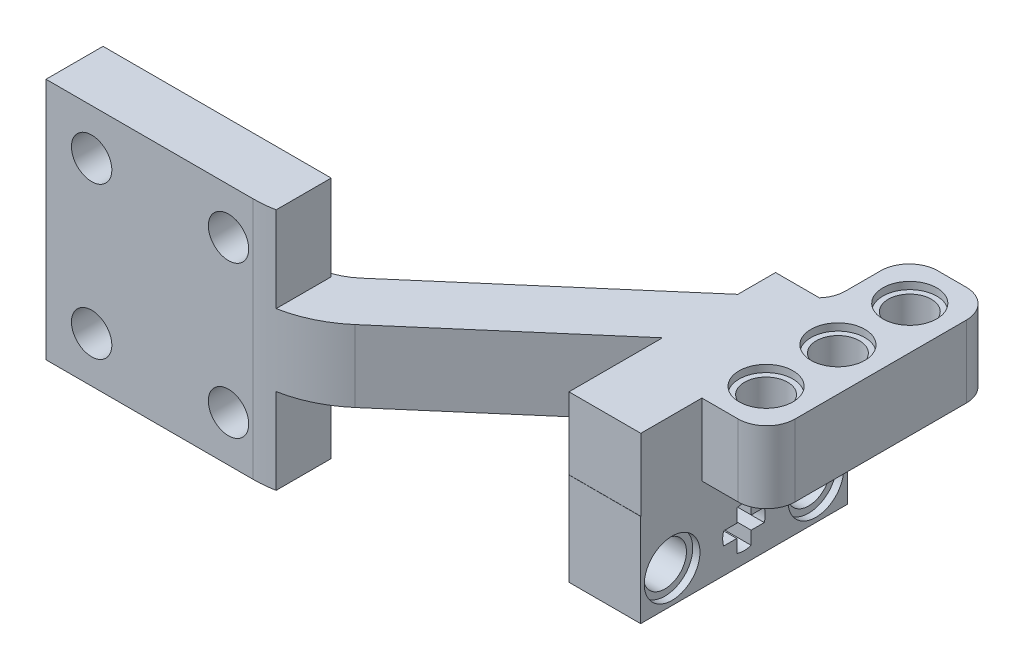
SolidWorks part; units mm, degrees
ref_plane "Front Plane" through (0, 0, 0) normal (0, 0, 1) x (1, 0, 0)
ref_plane "Top Plane" through (0, 0, 0) normal (0, 1, 0) x (1, 0, 0)
ref_plane "Right Plane" through (0, 0, 0) normal (1, 0, 0) x (0, 0, -1)
sketch "Sketch6" plane through (0, 0, 0) normal (0, 1, 0) x (1, 0, 0)
  line L1 (-4.7625, 12.7) -> (4.7625, 12.7)
  line L2 (-4.7625, 12.7) -> (-4.7625, -12.7)
  line L3 (-4.7625, -12.7) -> (4.7625, -12.7)
  line L4 (4.7625, 12.7) -> (4.7625, -12.7)
  line L5 (-4.7625, 12.7) -> (4.7625, -12.7) construction
  line L6 (-4.7625, -12.7) -> (4.7625, 12.7) construction
  point P0 (0, 0)
  dimension "D1" = 9.525
  dimension "D2" = 25.4
extrude "Boss-Extrude1" add sketch "Sketch6" against normal blind 8
sketch "Sketch16" plane through (0, 0, 0) normal (0, -1, 0) x (1, 0, 0)
  line L1 (-2.4423, -3.5) -> (-10.4423, -3.5)
  line L2 (-2.4423, -3.5) -> (-2.4423, 19.5)
  line L3 (-2.4423, 19.5) -> (-10.4423, 19.5)
  line L4 (-10.4423, -3.5) -> (-10.4423, 19.5)
  line L5 (-2.4423, -3.5) -> (-10.4423, 19.5) construction
  line L6 (-2.4423, 19.5) -> (-10.4423, -3.5) construction
  line L7 (-4.7625, -12.7) -> (-4.7625, 12.7) construction
  point P0 (-6.4423, 8)
  point P12 (-4.7625, 0)
  dimension "D1" = 6.4423
  dimension "D2" = 8
  dimension "D3" = 8
  dimension "D4" = 23
extrude "Boss-Extrude6" add sketch "Sketch16" along normal up to surface (8 mm away) up to face at (0, -8, 0)
sketch "Sketch7" plane through (0, 0, 0) normal (0, 1, 0) x (1, 0, 0)
  circle A0 centre (0, 8) radius 2.4
  circle A1 centre (0, 0) radius 2.4
  circle A2 centre (0, -8) radius 2.4
  circle A3 centre (0, 8) radius 3
  circle A4 centre (0, 0) radius 3
  circle A5 centre (0, -8) radius 3
  dimension "D3" = 4.8
  dimension "D1" = 8
  dimension "D2" = 8
  dimension "D4" = 0.6
extrude "Cut-Extrude1" cut sketch "Sketch7" against normal blind 0.8
extrude "Cut-Extrude2" cut sketch "Sketch7<3>" against normal blind 7.2 contours A0 | A1 | A2 region at (0, 0, -8) region at (0, 0, 0) region at (0, 0, 8)
sketch "Sketch7<3>" plane through (0, 0, 0) normal (0, 1, 0) x (1, 0, 0) same geometry as "Sketch7"
sketch "Sketch9" plane through (0, -7.2, -7.2) normal (0, 1, 0) x (1, 0, 0)
  circle A0 centre (0, 0.8) radius 2.4
  circle A1 centre (0, -7.2) radius 2.4
  circle A2 centre (0, -15.2) radius 2.4
  circle A3 centre (0, 0.8) radius 3
  circle A4 centre (0, -7.2) radius 3
  circle A5 centre (0, -15.2) radius 3
  dimension "D3" = 4.8
  dimension "D1" = 8
  dimension "D2" = 8
  dimension "D4" = 0.6
extrude "Cut-Extrude4" cut sketch "Sketch9" against normal blind 0.8 contours A3 | A4 | A5
ref_plane "Plane4" through (0, 0, 28) normal (0, 0, 1) x (1, 0, 0)
sketch "Sketch10" plane through (0, -8, 0) normal (0, -1, 0) x (-1, 0, 0)
  line L1 (4.7625, 4.1904) -> (34.7625, -21.65)
  line L2 (4.7625, 4.1904) -> (4.7625, -4.1904) construction
  line L3 (34.7625, -21.65) -> (60.1625, -21.65)
  line L4 (60.1625, -21.65) -> (60.1625, -28)
  line L5 (-57.9984, -28) -> (57.9984, -28) construction
  line L8 (4.7625, -4.1904) -> (32.4047, -28)
  line L10 (4.7625, 4.1904) -> (4.7625, -4.1904)
  line L14 (4.7625, 12.7) -> (4.7625, 3.5) construction
  line L18 (32.4047, -28) -> (60.1625, -28)
  point P2 (4.7625, 0)
  dimension "D1" = 30
  dimension "D2" = 6.35
  dimension "D3" = 25.4
  dimension "D4" = 6.35
extrude "Boss-Extrude3" add sketch "Sketch10" against normal up to surface (8 mm away) up to face at (0, 0, -5)
fillet "Fillet1" radius 3.175 1 edges at (-4.7625, -4, -4.1904)
fillet "Fillet3" radius 3.175 3 edges at (4.7625, -4, -12.7) (4.7625, -4, 12.7) (-4.7625, -4, -12.7)
sketch "Sketch18" plane through (0, 0, 0) normal (0, 1, 0) x (1, 0, 0)
  line L0 (-57.9984, -28) -> (57.9984, -28) construction
  line L1 (-60.1625, -21.65) -> (-34.7625, -21.65)
  line L2 (-60.1625, -21.65) -> (-60.1625, -28)
  line L3 (-60.1625, -28) -> (-34.7625, -28)
  line L4 (-34.7625, -21.65) -> (-34.7625, -28)
extrude "Boss-Extrude7" add sketch "Sketch18" along normal blind 9.525 and the other way blind 17.525
fillet "Fillet6" radius 12.7 1 edges at (-32.4047, -4, 28)
fillet "Fillet7" radius 6.35 1 edges at (-34.7625, -4, 21.65)
sketch "Sketch11" plane through (0, -8, 0) normal (0, -1, 0) x (-1, 0, 0)
  line L0 (4.7625, 9.525) -> (4.7625, 5.6089) construction
  line L1 (10.4422, -19.5186) -> (2.4422, -19.5186)
  line L2 (10.4422, -19.5186) -> (10.4422, 3.4814)
  line L3 (10.4422, 3.4814) -> (2.4422, 3.4814)
  line L4 (2.4422, -19.5186) -> (2.4422, 3.4814)
  line L5 (10.4422, -19.5186) -> (2.4422, 3.4814) construction
  line L6 (10.4422, 3.4814) -> (2.4422, -19.5186) construction
  point P0 (6.4422, -8.0186)
  point P9 (4.7625, 7.5669)
  dimension "D1" = 6.4422
  dimension "D2" = 15.5855
  dimension "D3" = 8
  dimension "D4" = 23
extrude "Boss-Extrude4" add sketch "Sketch11" along normal blind 6.7462 contours L4 L3 L2 L1
sketch "Sketch13" plane through (-2.4423, 0, 0) normal (1, 0, 0) x (0, 0, -1)
  line L0 (-19.5186, -14.7462) -> (3.4814, -14.7462) construction
  line L1 (-8.8186, -14.0148) -> (-8.8186, -12.5521)
  line L2 (-7.2186, -12.5521) -> (-7.2186, -14.0148)
  line L3 (-8.8186, -14.0148) -> (-7.2186, -14.0148) construction
  line L4 (-8.8186, -14.0148) -> (-8.8186, -15.4775) construction
  line L5 (-8.8186, -14.0148) -> (-10.2813, -14.0148)
  line L6 (-10.2813, -15.4775) -> (-8.8186, -15.4775)
  line L7 (-8.8186, -15.4775) -> (-8.8186, -16.9403)
  line L8 (-7.2186, -16.9403) -> (-7.2186, -15.4775)
  line L9 (-7.2186, -15.4775) -> (-5.7558, -15.4775)
  line L10 (-7.2186, -14.0148) -> (-5.7558, -14.0148)
  line L11 (-5.7558, -14.0148) -> (-5.9183, -14.0148)
  circle A0 centre (-8.0186, -14.7462) radius 2.5157 construction
  circle A1 centre (-16.0186, -14.7462) radius 3.1
  circle A2 centre (-0.0186, -14.7462) radius 3.1
  circle A3 centre (-16.0186, -14.7462) radius 2.4
  circle A4 centre (-0.0186, -14.7462) radius 2.4
  arc A5 (-8.8186, -12.5521) -> (-7.2186, -12.5521) centre (-8.0186, -15.0259) cw
  arc A6 (-10.2813, -14.0148) -> (-10.2813, -15.4775) centre (-7.7863, -14.7462) ccw
  arc A7 (-8.8186, -16.9403) -> (-7.2186, -16.9403) centre (-8.0186, -14.4664) ccw
  arc A8 (-5.7558, -14.0148) -> (-5.7558, -15.4775) centre (-8.2509, -14.7462) cw
  point P14 (-8.0186, -14.0148)
  point P16 (-8.8186, -14.7462)
  line M4 (-19.5186, -14.7462) -> (3.4814, -14.7462)
  dimension "D1" = 6.2
  dimension "D2" = 4.8
  dimension "D7" = 2.6
  dimension "D3" = 8
  dimension "D4" = 8
  dimension "D5" = 1.4627
  dimension "D6" = 1.6
sketch "Sketch14" plane through (0, -14.7462, 0) normal (0, -1, 0) x (-1, 0, 0)
  line L1 (10.4422, -19.5186) -> (2.4422, -19.5186)
  line L2 (10.4422, -19.5186) -> (10.4422, 3.4814)
  line L3 (10.4422, 3.4814) -> (2.4422, 3.4814)
  line L4 (2.4422, -19.5186) -> (2.4422, 3.4814)
extrude "Boss-Extrude5" add sketch "Sketch14" along normal blind 3.6 contours L2 L3 L4 L1
extrude "Cut-Extrude5" cut sketch "Sketch13" against normal blind 0.8 contours A3 A1 M4 | A3 A1 M4 | A8 A6 L6 L7 A7 L8 L9 M4 | A8 L10 L2 A5 L1 L5 A6 M4 | A4 A2 M4 | A4 A2 M4 region at (-2.4423, -11.7155, 0.0186) region at (-2.4423, -14.8155, 2.7686) region at (-2.4423, -17.7768, 16.0186) region at (-2.4423, -14.6768, 13.2686) region at (-2.4423, -13.9029, 8.0186) region at (-2.4423, -15.5895, 8.0186)
extrude "Cut-Extrude6" cut sketch "Sketch13<3>" against normal through all contours A8 A6 L6 L7 A7 L8 L9 M4 | A8 L10 L2 A5 L1 L5 A6 M4 | A4 M4 | A4 M4 | A3 region at (-2.4423, -13.9029, 8.0186) region at (-2.4423, -15.5895, 8.0186) region at (-2.4423, -15.7648, 0.0186) region at (-2.4423, -13.7276, 0.0186)
sketch "Sketch13<3>" plane through (-2.4423, 0, 0) normal (1, 0, 0) x (0, 0, -1) same geometry as "Sketch13"
ref_plane "Plane5" through (-6.4423, 0, 0) normal (1, 0, 0) x (0, 0, -1)
mirror "Mirror1" about plane through (-6.4423, 0, 0) normal (1, 0, 0) of "Cut-Extrude5"
hole_wizard "#8 Clearance Hole1" positions "Sketch19" profile "Sketch20" hole size "#8" standard "ANSI Inch" end condition through all
sketch "Sketch19" plane through (0, 0, 21.65) normal (0, 0, -1) x (-1, 0, 0)
  line L0 (34.7625, 0) -> (34.7625, 9.525) construction
  line L1 (34.7625, 9.525) -> (60.1625, 9.525) construction
  line L2 (60.1625, 9.525) -> (60.1625, -17.525) construction
  line L3 (34.7625, -17.525) -> (60.1625, -17.525) construction
  point P0 (55.0825, 4.445)
  point P2 (39.8425, 4.445)
  point P4 (39.8425, -12.445)
  point P6 (55.0825, -12.445)
  dimension "D1" = 5.08
  dimension "D2" = 5.08
  dimension "D3" = 5.08
  dimension "D4" = 5.08
sketch "Sketch20" plane through (-55.0825, 4.445, 21.65) normal (1, 0, 0) x (0, 1, 0)
  line L0 (0, 0) -> (0, 6.35)
  line L1 (0, 6.35) -> (2.2479, 6.35)
  line L2 (2.2479, 6.35) -> (2.2479, 0)
  line L5 (2.2479, 0) -> (0, 0)
  line L11 (0, -6.35) -> (0, 107.95) construction
  dimension "Thru Hole Dia." = 4.4958
  dimension "Thru Hole Depth" = 6.35
